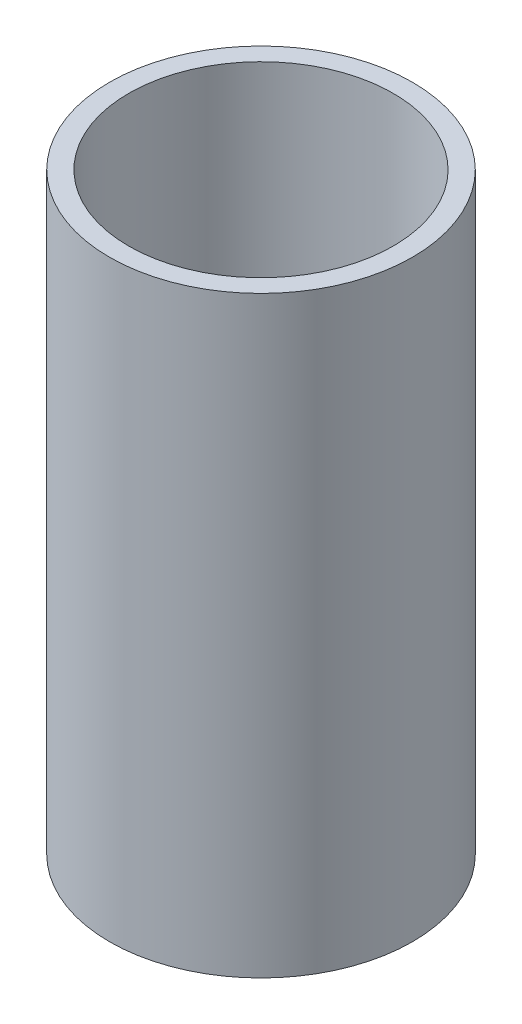
SolidWorks part; units mm, degrees
ref_plane "Front Plane" through (0, 0, 0) normal (0, 0, 1) x (1, 0, 0)
ref_plane "Top Plane" through (0, 0, 0) normal (0, 1, 0) x (1, 0, 0)
ref_plane "Right Plane" through (0, 0, 0) normal (1, 0, 0) x (0, 0, -1)
sketch "Sketch1" plane through (0, 0, 0) normal (0, 1, 0) x (1, 0, 0)
  circle A0 centre (0, 0) radius 35
  dimension "SLEEVE_OD" = 70
extrude "Boss-Extrude1" add sketch "Sketch1" along normal blind 136.941
sketch "Sketch2" plane through (0, 0, 0) normal (0, 1, 0) x (1, 0, 0)
  circle A0 centre (0, 0) radius 30.5608
  dimension "BORE_D" = 61.1216
extrude "Cut-Extrude1" cut sketch "Sketch2" along normal through all
chamfer "Chamfer1" distance 2.7081 angle 65.551 rebuild error yes
